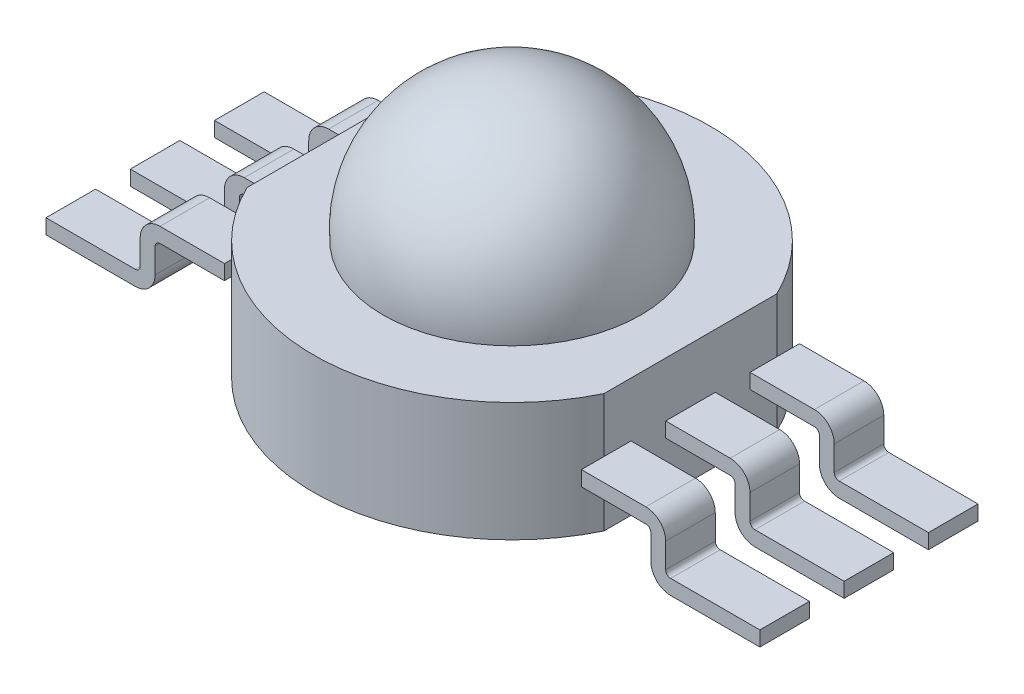
SolidWorks part; units mm, degrees
material "ABS"
ref_plane "Front Plane" through (0, 0, 0) normal (0, 0, 1) x (1, 0, 0)
ref_plane "Top Plane" through (0, 0, 0) normal (0, 1, 0) x (1, 0, 0)
ref_plane "Right Plane" through (0, 0, 0) normal (1, 0, 0) x (0, 0, -1)
sketch "Sketch1" plane through (0, 0, 0) normal (0, 1, 0) x (1, 0, 0)
  line L0 (-3.6, 1.7436) -> (-3.6, -1.7436)
  line L1 (3.6, 1.7436) -> (3.6, -1.7436)
  arc A0 (3.6, 1.7436) -> (-3.6, 1.7436) centre (0, 0) ccw
  arc A1 (-3.6, -1.7436) -> (3.6, -1.7436) centre (0, 0) ccw
  dimension "D1" = 8
  dimension "D2" = 7.2
extrude "LED Base Boss-Extrude1" add sketch "Sketch1" along normal blind 2.4
sketch "Sketch3" plane through (0, 0, 0) normal (0, 0, 1) x (1, 0, 0)
  line L0 (0, 0) -> (0, 5.0961) construction
  line L1 (3.6, 2.4) -> (-3.6, 2.4) construction
  line L2 (0, 5.2) -> (2.6, 5.2) construction
  line L3 (2.6, 2.4) -> (2.6, 5.2) construction
  line L4 (2.6, 2.4) -> (0, 2.4)
  line L5 (0, 5.2) -> (0, 2.4)
  arc A0 (0, 5.2) -> (2.6, 2.4) centre (0, 2.5929) cw
  dimension "D1" = 2.6
  dimension "D2" = 5.2
revolve "LED Lens Revolve2" add sketch "Sketch3" angle 360 about L5
sketch "Sketch4" plane through (0, 0, 0) normal (0, 0, 1) x (1, 0, 0)
  line L0 (3.6, 2.4) -> (3.6, 0) construction
  line L1 (3.6, 1.3) -> (4.9, 1.3)
  line L2 (3.6, 1.3) -> (3.6, 1)
  line L3 (3.6, 1) -> (4.9, 1)
  line L4 (5, 0.9) -> (5, 0.4)
  line L5 (5.3, 0.9) -> (5.3, 0.4)
  line L6 (4.9, 1.3) -> (4.9, 1) construction
  line L7 (5.4, 0.3) -> (5.4, 0) construction
  line L8 (5, 0.65) -> (5.3, 0.65) construction
  line L9 (-3.6, 0) -> (3.6, 0) construction
  line L10 (5.4, 0) -> (7.2, 0)
  line L12 (5.4, 0.3) -> (7.2, 0.3)
  line L13 (7.2, 0) -> (7.2, 0.3)
  arc A0 (4.9, 1.3) -> (5.3, 0.9) centre (4.9, 0.9) cw
  arc A1 (4.9, 1) -> (5, 0.9) centre (4.9, 0.9) cw
  arc A2 (5, 0.4) -> (5.4, 0) centre (5.4, 0.4) ccw
  arc A3 (5.3, 0.4) -> (5.4, 0.3) centre (5.4, 0.4) ccw
  dimension "D1" = 3.6
  dimension "D2" = 0.3
  dimension "D3" = 1.3
  dimension "D4" = 0
  dimension "D5" = 0.5
  dimension "D6" = 1.3
  dimension "D7" = 1.8
extrude "Pin Right Boss-Extrude2" add sketch "Sketch4" along normal blind 2.2 and the other way blind 2.2
sketch "Sketch5" plane through (0, 1.3, 0) normal (0, 1, 0) x (1, 0, 0)
  line L0 (3.6, -1.7436) -> (3.6, 1.7436) construction
  line L1 (3.6, 1.2) -> (7.2, 1.2)
  line L2 (3.6, 1.2) -> (3.6, 0.5)
  line L3 (3.6, 0.5) -> (7.2, 0.5)
  line L4 (7.2, 1.2) -> (7.2, 0.5)
  line L5 (7.2, 2.2) -> (7.2, -2.2) construction
  line L6 (0, 0) -> (1.3969, 0) construction
  line L7 (7.2, -0.5) -> (3.6, -0.5)
  line L8 (7.2, -0.5) -> (7.2, -1.2)
  line L9 (7.2, -1.2) -> (3.6, -1.2)
  line L10 (3.6, -0.5) -> (3.6, -1.2)
  line L11 (3.6, -0.5) -> (3.6, 0) construction
  line L12 (3.6, 1.7436) -> (3.6, -1.7436) construction
  line L13 (3.6, 0) -> (3.6, 0.5) construction
  line L14 (7.2, 2.2) -> (7.2, 1.2) construction
  line L15 (7.2, 0.5) -> (7.2, -0.5) construction
  line L16 (7.2, -1.2) -> (7.2, -2.2) construction
  dimension "D1" = 0.7
  dimension "D2" = 1
extrude "Pin Right Space Cut-Extrude1" cut sketch "Sketch5" against normal up to surface (1.3 mm away) up to face at (6.3, 0, 0)
mirror "Pin Left Mirror1" about plane through (0, 0, 0) normal (1, 0, 0) of "Pin Right Space Cut-Extrude1", "Pin Right Boss-Extrude2"
sketch "Sketch6" plane through (0, 0, 0) normal (0, -1, 0) x (1, 0, 0)
  circle A0 centre (0, 0) radius 2.95
  dimension "D1" = 5.9
extrude "Heatsink Boss-Extrude3" add sketch "Sketch6" along normal blind 0.1
equation "\"D1@Sketch3\"=5.2/2"
equation "\"D1@Sketch4\"=(14.40-7.2)/2"
equation "\"D1@Pin Right Boss-Extrude2\"=(1+0.7+1+0.7+1)/2"
equation "\"D2@Pin Right Boss-Extrude2\"=(1+0.7+1+0.7+1)/2"
